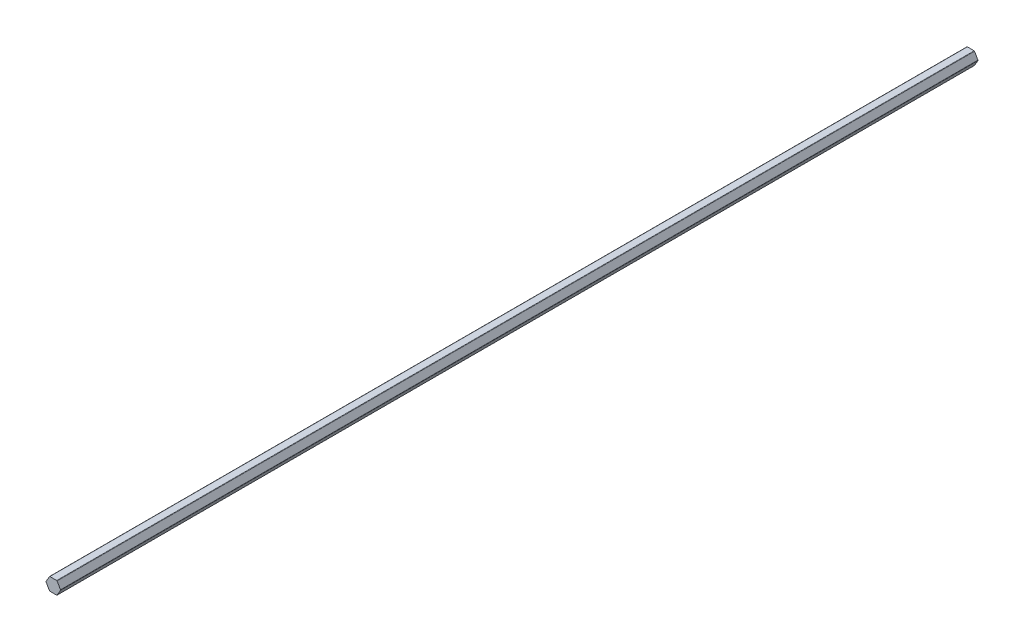
SolidWorks part; units mm, degrees
material "7075-T6 (SN)"
ref_plane "Front Plane" through (0, 0, 0) normal (0, 0, 1) x (1, 0, 0)
ref_plane "Top Plane" through (0, 0, 0) normal (0, 1, 0) x (1, 0, 0)
ref_plane "Right Plane" through (0, 0, 0) normal (1, 0, 0) x (0, 0, -1)
sketch "Sketch1" plane through (0, 0, 0) normal (0, 0, 1) x (1, 0, 0)
  line L1 (7.3323, 0) -> (3.6662, 6.35)
  line L2 (3.6662, 6.35) -> (-3.6662, 6.35)
  line L3 (-3.6662, 6.35) -> (-7.3323, 0)
  line L4 (-7.3323, 0) -> (-3.6662, -6.35)
  line L5 (-3.6662, -6.35) -> (3.6662, -6.35)
  line L6 (3.6662, -6.35) -> (7.3323, 0)
  circle A0 centre (0, 0) radius 6.35 construction
  dimension "D1" = 12.7
extrude "Boss-Extrude1" add sketch "Sketch1" along normal mid plane 914.4
fillet "Fillet1" radius 0.508 6 edges at (-3.6662, -6.35, 0) (-7.3323, 0, 0) (3.6662, -6.35, 0) (7.3323, 0, 0) (-3.6662, 6.35, 0) (3.6662, 6.35, 0)
ref_axis "Axis1" through (0, 0, 83.82) along (0, 0, -1)
